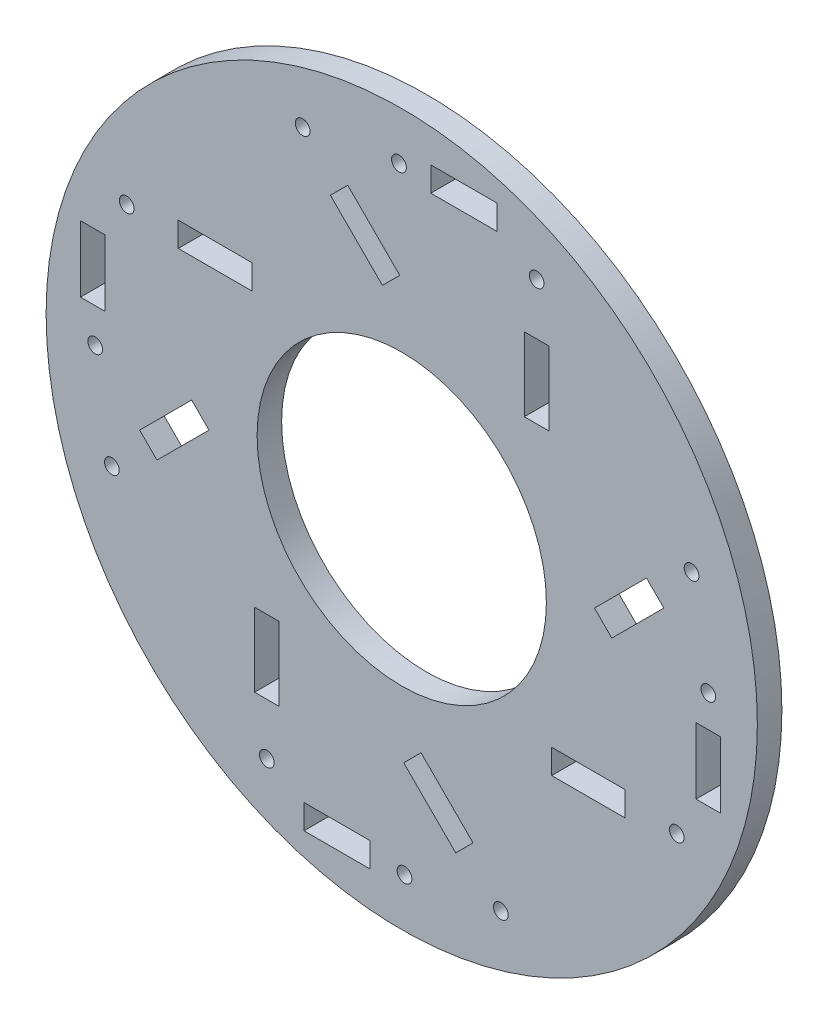
SolidWorks part; units mm, degrees
ref_plane "Front Plane" through (0, 0, 0) normal (0, 0, 1) x (1, 0, 0)
ref_plane "Top Plane" through (0, 0, 0) normal (0, 1, 0) x (1, 0, 0)
ref_plane "Right Plane" through (0, 0, 0) normal (1, 0, 0) x (0, 0, -1)
sketch "Sketch1" plane through (0, 0, 0) normal (0, 0, 1) x (1, 0, 0)
  line L0 (39.2907, 3.9354) -> (49.8973, 14.542)
  line L1 (25, 30.5655) -> (30, 30.5655)
  line L2 (25, 30.5655) -> (25, 45.5655)
  line L3 (25, 45.5655) -> (30, 45.5655)
  line L4 (30, 30.5655) -> (30, 45.5655)
  line L5 (39.2907, 3.9354) -> (42.8263, 0.3999)
  line L6 (42.8263, 0.3999) -> (53.4329, 11.0065)
  line L7 (49.8973, 14.542) -> (53.4329, 11.0065)
  line L8 (30.5655, -25) -> (45.5655, -25)
  line L9 (30.5655, -25) -> (30.5655, -30)
  line L10 (30.5655, -30) -> (45.5655, -30)
  line L11 (45.5655, -25) -> (45.5655, -30)
  line L12 (3.9354, -39.2907) -> (14.542, -49.8973)
  line L13 (3.9354, -39.2907) -> (0.3999, -42.8263)
  line L14 (0.3999, -42.8263) -> (11.0065, -53.4329)
  line L15 (14.542, -49.8973) -> (11.0065, -53.4329)
  line L16 (-25, -30.5655) -> (-25, -45.5655)
  line L17 (-25, -30.5655) -> (-30, -30.5655)
  line L18 (-30, -30.5655) -> (-30, -45.5655)
  line L19 (-25, -45.5655) -> (-30, -45.5655)
  line L20 (-39.2907, -3.9354) -> (-49.8973, -14.542)
  line L21 (-39.2907, -3.9354) -> (-42.8263, -0.3999)
  line L22 (-42.8263, -0.3999) -> (-53.4329, -11.0065)
  line L23 (-49.8973, -14.542) -> (-53.4329, -11.0065)
  line L24 (-30.5655, 25) -> (-45.5655, 25)
  line L25 (-30.5655, 25) -> (-30.5655, 30)
  line L26 (-30.5655, 30) -> (-45.5655, 30)
  line L27 (-45.5655, 25) -> (-45.5655, 30)
  line L28 (-3.9354, 39.2907) -> (-14.542, 49.8973)
  line L29 (-3.9354, 39.2907) -> (-0.3999, 42.8263)
  line L30 (-0.3999, 42.8263) -> (-11.0065, 53.4329)
  line L31 (-14.542, 49.8973) -> (-11.0065, 53.4329)
  line L32 (27.5, 56.0655) -> (27.5, 45.5655) construction
  line L33 (-19.9345, -65) -> (-19.9345, -60)
  line L34 (65, -19.4345) -> (60, -19.4345)
  line L35 (65, -19.4345) -> (65, -5.9345)
  line L36 (65, -5.9345) -> (60, -5.9345)
  line L37 (60, -19.4345) -> (60, -5.9345)
  line L38 (-19.9345, -65) -> (-6.4345, -65)
  line L39 (-19.9345, -60) -> (-6.4345, -60)
  line L40 (-6.4345, -65) -> (-6.4345, -60)
  line L41 (-65.5, 19.9345) -> (-60.5, 19.9345)
  line L42 (-65.5, 19.9345) -> (-65.5, 6.4345)
  line L43 (-60.5, 19.9345) -> (-60.5, 6.4345)
  line L44 (-65.5, 6.4345) -> (-60.5, 6.4345)
  line L45 (19.4345, 65.5) -> (19.4345, 60.5)
  line L46 (19.4345, 65.5) -> (5.9345, 65.5)
  line L47 (19.4345, 60.5) -> (5.9345, 60.5)
  line L48 (5.9345, 65.5) -> (5.9345, 60.5)
  line L49 (62.5, -5.9345) -> (62.5, 0.5655) construction
  circle A0 centre (0, 0) radius 58.6265 construction
  circle A1 centre (0, 0) radius 72.5
  circle A2 centre (27.5, 56.0655) radius 1.5
  circle A3 centre (59.0897, 20.1989) radius 1.5
  circle A4 centre (56.0655, -27.5) radius 1.5
  circle A5 centre (20.1989, -59.0897) radius 1.5
  circle A6 centre (-27.5, -56.0655) radius 1.5
  circle A7 centre (-59.0897, -20.1989) radius 1.5
  circle A8 centre (-56.0655, 27.5) radius 1.5
  circle A9 centre (-20.1989, 59.0897) radius 1.5
  circle A10 centre (62.5, 0.5655) radius 1.5
  circle A11 centre (0.5655, -62.5) radius 1.5
  circle A12 centre (-62.5, -0.5655) radius 1.5
  circle A13 centre (-0.5655, 62.5) radius 1.5
  dimension "D1" = 145
  dimension "D4" = 3
  dimension "D6" = 10.5
  dimension "D13" = 3
  dimension "D3" = 15
  dimension "D7" = 13.5
  dimension "D8" = 5
  dimension "D9" = 50
  dimension "D10" = 30
  dimension "D12" = 6.5
  dimension "D2" = 8
  dimension "D5" = 8
  dimension "D11" = 4
  dimension "D14" = 4
extrude "Boss-Extrude1" add sketch "Sketch1" along normal blind 5 contours L7 A1 L4 L1 L2 L3 L30 L29 L28 L31 L26 L25 L24 L27 L22 L21 L20 L23 L18 L17 L16 L19 L14 L13 L12 L15 L10 L9 L8 L11 L6 L5 L0 region at (0.0043, -0.0043, 0)
sketch "Sketch2" plane through (0, 0, 5) normal (0, 0, 1) x (1, 0, 0)
  circle A0 centre (0, 0) radius 39.4873 construction
  circle A1 centre (0, 0) radius 29.4873
  dimension "D1" = 10
extrude "Cut-Extrude1" cut sketch "Sketch2" against normal blind 10
